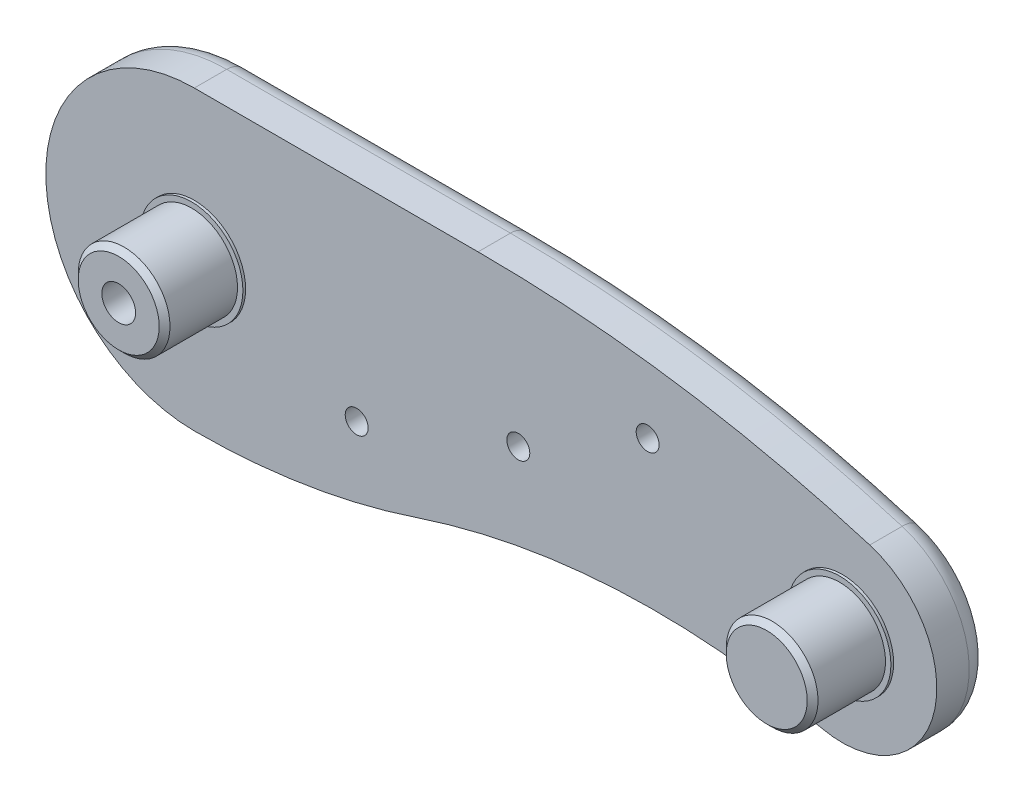
SolidWorks part; units mm, degrees
ref_plane "Front Plane" through (0, 0, 0) normal (0, 0, 1) x (1, 0, 0)
ref_plane "Top Plane" through (0, 0, 0) normal (0, 1, 0) x (1, 0, 0)
ref_plane "Right Plane" through (0, 0, 0) normal (1, 0, 0) x (0, 0, -1)
sketch "Sketch1" plane through (0, 0, 0) normal (0, 0, 1) x (1, 0, 0)
  line L0 (0, 27.5) -> (52.5463, 27.5)
  line L1 (0, 0) -> (120, 0) construction
  line L2 (0, 0) -> (0, -27.5) construction
  circle A0 centre (0, 0) radius 27.5
  circle A1 centre (120, 0) radius 17.5
  arc A2 (52.5463, 27.5) -> (125.0772, 16.7473) centre (52.5463, -222.5) cw
  arc A3 (116.1527, -17.0719) -> (41.1063, -20.8299) centre (85.3746, -153.6468) ccw
  arc A4 (0, -27.5) -> (41.1063, -20.8299) centre (0, 102.5) ccw
  dimension "D1" = 55
  dimension "D3" = 35
  dimension "D4" = 130
  dimension "D5" = 140
  dimension "D6" = 250
  dimension "D2" = 120
extrude "Boss-Extrude1" add sketch "Sketch1" along normal blind 6 contours A0 A4 A3 A1 A2 L0 | A0 | A1 region at (61.3869, 4.6825, 0) region at (0, 0, 0) region at (120, 0, 0)
sketch "Sketch3" plane through (0, 0, 0) normal (0, 0, -1) x (-1, 0, 0)
  circle A0 centre (0, 0) radius 10
  circle A1 centre (0, 0) radius 27.5
  arc A2 (0, -27.5) -> (0, 27.5) centre (0, 0) ccw construction
  line M1 (0, 27.5) -> (-52.5463, 27.5)
  arc M2 (-52.5463, 27.5) -> (-125.0772, 16.7473) centre (-52.5463, -222.5) ccw
  arc M3 (-125.0772, 16.7473) -> (-116.1527, -17.0719) centre (-120, 0) ccw
  arc M4 (-116.1527, -17.0719) -> (-41.1063, -20.8299) centre (-85.3746, -153.6468) cw
  arc M5 (-41.1063, -20.8299) -> (0, -27.5) centre (0, 102.5) ccw
  arc M6 (0, -27.5) -> (0, 27.5) centre (0, 0) ccw
  dimension "D1" = 20
extrude "Boss-Extrude3" add sketch "Sketch3" along normal blind 4 contours A1 M1 M2 M3 M4 M5 | A1 A0 M6 region at (-18.8954, -18.8954, 0) region at (73.4928, 3.7154, 0)
sketch "Sketch4" plane through (0, 0, 6) normal (0, 0, 1) x (1, 0, 0)
  circle A0 centre (0, 0) radius 8.5
  circle A1 centre (120, 0) radius 8.5
  dimension "D1" = 17
  dimension "D2" = 17
extrude "Boss-Extrude4" add sketch "Sketch4" along normal blind 14
sketch "Sketch5" plane through (0, 0, -4) normal (0, 0, -1) x (-1, 0, 0)
  line L0 (0, 0) -> (-60, 0) construction
  line L1 (0, 0) -> (-83.9535, 13.2969) construction
  line L2 (0, 0) -> (-30.0702, -10.9446) construction
  circle A0 centre (-83.9535, 13.2969) radius 2.125
  circle A1 centre (-60, 0) radius 2.125
  circle A2 centre (-30.0702, -10.9446) radius 2.125
  dimension "D6" = 4.25
  dimension "D1" = 20
  dimension "D2" = 9
  dimension "D3" = 85
  dimension "D4" = 60
  dimension "D5" = 32
extrude "Cut-Extrude1" cut sketch "Sketch5" against normal through all
sketch "Sketch6" plane through (0, 0, -4) normal (0, 0, -1) x (-1, 0, 0)
  circle A0 centre (-83.9535, 13.2969) radius 3.75
  circle A1 centre (-60, 0) radius 3.75
  circle A2 centre (-30.0702, -10.9446) radius 3.75
  dimension "D1" = 7.5
extrude "Cut-Extrude2" cut sketch "Sketch6" against normal blind 4.25
fillet "Fillet1" radius 4 6 edges at (-27.5, 0, -4) (20.822, -25.8216, -4) (78.3727, -13.822, -4) (136.9208, -4.4652, -4) (89.2081, 24.7972, -4) (26.2732, 27.5, -4)
sketch "Sketch7" plane through (0, 0, 6) normal (0, 0, 1) x (1, 0, 0)
  circle A0 centre (0, 0) radius 9.5
  circle A1 centre (0, 0) radius 8.5 construction
  circle A2 centre (120, 0) radius 9.5
  circle A3 centre (0, 0) radius 8.5
  circle A4 centre (0, 0) radius 8.5
  circle A5 centre (120, 0) radius 8.5 construction
  circle A6 centre (120, 0) radius 8.5
  dimension "D1" = 1
  dimension "D3" = 1
  dimension "D2" = 0
extrude "Boss-Extrude5" add sketch "Sketch7" along normal blind 0.5
chamfer "Chamfer2" distance 1 angle 45 2 edges at (8.5, 0, 20) (128.5, 0, 20)
sketch "Sketch8" plane through (0, 0, 0) normal (0, 0, -1) x (-1, 0, 0)
  circle A0 centre (0, 0) radius 1.625
  dimension "D1" = 3.25
extrude "Cut-Extrude3" cut sketch "Sketch8" against normal through all
sketch "Sketch9" plane through (0, 0, 20) normal (0, 0, 1) x (1, 0, 0)
  circle A0 centre (0, 0) radius 3.125
  dimension "D1" = 6.25
extrude "Cut-Extrude4" cut sketch "Sketch9" against normal blind 17
